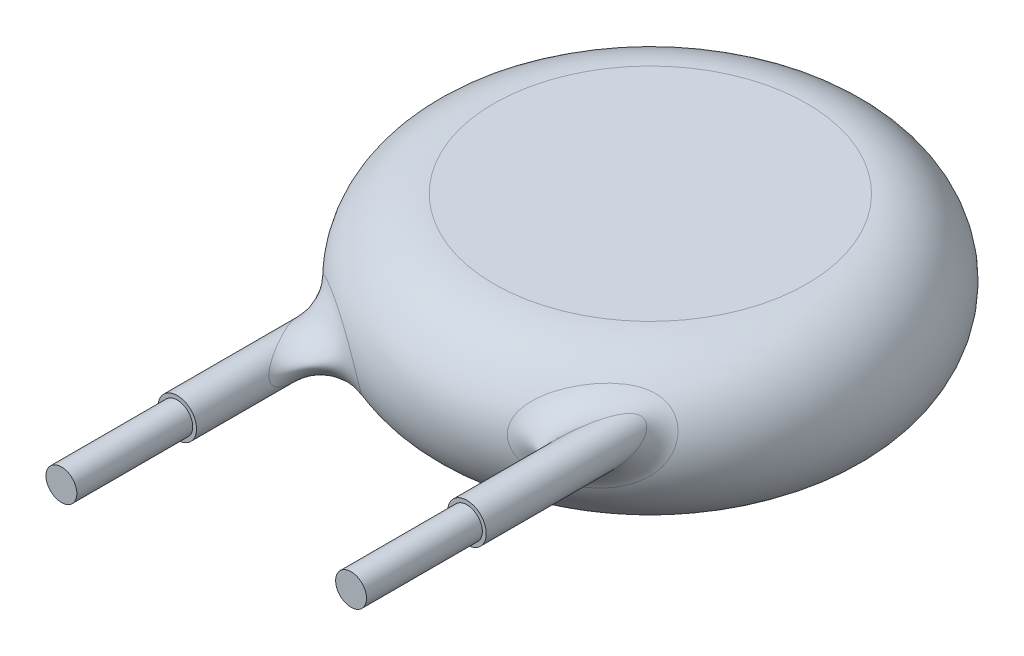
SolidWorks part; units mm, degrees
ref_plane "Front Plane" through (0, 0, 0) normal (0, 0, 1) x (1, 0, 0)
ref_plane "Top Plane" through (0, 0, 0) normal (0, 1, 0) x (1, 0, 0)
ref_plane "Right Plane" through (0, 0, 0) normal (1, 0, 0) x (0, 0, -1)
sketch "Sketch1" plane through (0, 0, 0) normal (0, 0, 1) x (1, 0, 0)
  line L0 (0, 12.9726) -> (0, -9.7806) construction
  line L1 (4.05, 1.95) -> (0, 1.95)
  line L2 (0, 1.95) -> (0, -1.95)
  line L3 (0, -1.95) -> (4.05, -1.95)
  arc A0 (4.05, -1.95) -> (4.05, 1.95) centre (4.05, 0) ccw
  dimension "D1" = 3.9
  dimension "D2" = 12
  dimension "D3" = 1.95
revolve "Revolve1" add sketch "Sketch1" angle 360 about L0
ref_plane "Plane1" through (0, 0, -6) normal (0, 0, 1) x (1, 0, 0)
ref_plane "Plane2" through (0, 0, 8.5) normal (0, 0, 1) x (1, 0, 0)
sketch "Sketch3" plane through (0, 0, 8.5) normal (0, 0, 1) x (1, 0, 0)
  line L0 (-8.004, 0) -> (8.0735, 0) construction
  line L1 (0, 6.2434) -> (0, -6.2434) construction
  circle A0 centre (3.75, 0.7) radius 0.5
  circle A1 centre (-3.75, -0.7) radius 0.5
  point P9 (0, 0)
  dimension "D1" = 1
  dimension "D2" = 3.75
  dimension "D3" = 7.5
  dimension "D4" = 0.7
  dimension "D5" = 1.4
extrude "Extrude1" add sketch "Sketch3" against normal up to next
fillet "Fillet1" radius 1 2 edges at (-3.374, -0.3704, 4.9185) (3.3694, 0.3757, 4.9203)
sketch "Sketch4" plane through (0, 0, 8.5) normal (0, 0, 1) x (1, 0, 0)
  circle A0 centre (3.75, 0.7) radius 0.4
  circle A1 centre (-3.75, -0.7) radius 0.4
  dimension "D1" = 0.8
extrude "Extrude2" add sketch "Sketch4" along normal blind 3
